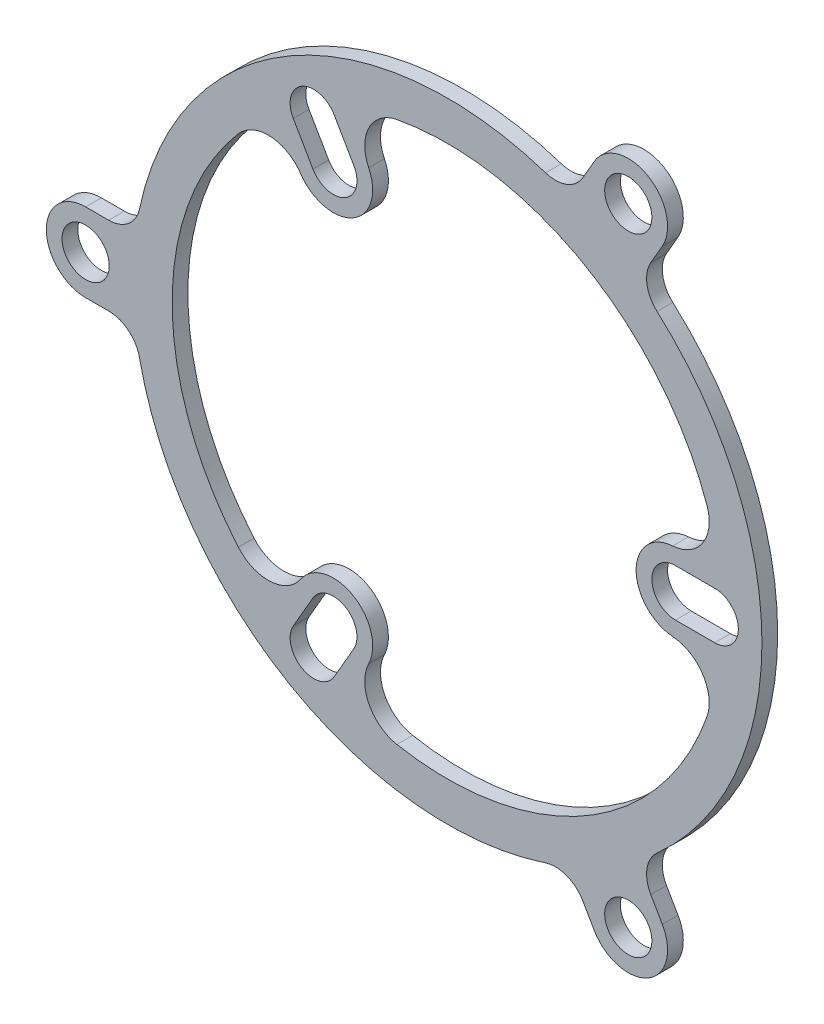
SolidWorks part; units mm, degrees
note: '?' marks a value the reader was unsure of.
material "1060 Alloy"
ref_plane "Front Plane" through (0, 0, 0) normal (0, 0, 1) x (1, 0, 0)
ref_plane "Top Plane" through (0, 0, 0) normal (0, 1, 0) x (1, 0, 0)
ref_plane "Right Plane" through (0, 0, 0) normal (1, 0, 0) x (0, 0, -1)
sketch "Sketch1" plane through (0, 0, 0) normal (0, 0, 1) x (1, 0, 0)
  circle A0 centre (0, 0) radius 40
  circle A1 centre (0, 0) radius 35
  dimension "D1" = 80
  dimension "D2" = 5
extrude "Boss-Extrude1" add sketch "Sketch1" along normal blind 2
sketch "Sketch2" plane through (0, 0, 0) normal (0, 0, -1) x (-1, 0, 0)
  line L0 (0, 0) -> (-40, 0) construction
  line L1 (-34, -3) -> (-29, -3)
  line L2 (-34, 3) -> (-29, 3)
  line L3 (-29, -5) -> (-34.641, -5)
  line L4 (-29, 5) -> (-34.641, 5)
  line L5 (-34.641, -5) -> (-37, -5)
  line L6 (-37, -5) -> (-37, 5)
  line L7 (-37, 5) -> (-34.641, 5)
  circle A0 centre (0, 0) radius 40 construction
  arc A1 (-34, 3) -> (-34, -3) centre (-34, 0) ccw
  arc A2 (-29, -3) -> (-29, 3) centre (-29, 0) ccw
  circle A3 centre (0, 0) radius 35 construction
  arc A4 (-29, -5) -> (-29, 5) centre (-29, 0) ccw
  circle M9 centre (0, 0) radius 35
  dimension "D1" = 6
  dimension "D2" = 34
  dimension "D3" = 5
  dimension "D4" = 2
extrude "Boss-Extrude2" add sketch "Sketch2" against normal blind 2 contours A4 L0 A2 L1 L3 M9 | L0 A4 L4 L2 A2 M9
sketch "Sketch3" plane through (0, 0, 0) normal (0, 0, -1) x (-1, 0, 0)
  circle A0 centre (-34, 0) radius 3
  arc A1 (-34, 3) -> (-34, -3) centre (-34, 0) ccw construction
  dimension "D1" = 6
extrude "Cut-Extrude1" cut sketch "Sketch3" against normal blind 2
fillet "Fillet1" radius 5 2 edges at (34.641, -5, 1) (34.641, 5, 1)
ref_axis "Axis1" through (0, 0, 2) along (0, 0, -1)?
pattern_circular "CirPattern1" count 3 over 360 about axis through (0, 0, 0) along (0, 0, 1) of "Boss-Extrude2", "Cut-Extrude1", "Fillet1"
sketch "Sketch4" plane through (0, 0, 0) normal (0, 0, -1) x (-1, 0, 0)
  line L0 (0, 0) -> (-40, 0) construction
  line L1 (0, 0) -> (20, 34.641) construction
  line L2 (0, 0) -> (-20, 34.641) construction
  line L3 (-20, 34.641) -> (-23, 39.8372) construction
  line L4 (-18.6699, 42.3372) -> (-15.513, 36.8693)
  line L5 (-27.3301, 37.3372) -> (-24.1733, 31.8693)
  line L6 (-27.3301, 37.3372) -> (-18.6699, 42.3372)
  line L7 (-24.1733, 31.8693) -> (-15.513, 36.8693)
  circle A0 centre (0, 0) radius 40 construction
  circle A1 centre (-23, 39.8372) radius 3
  arc A2 (-18.6699, 42.3372) -> (-27.3301, 37.3372) centre (-23, 39.8372) ccw
  circle M29 centre (0, 0) radius 40
  dimension "D3" = 6
  dimension "D5" = 2
  dimension "D1" = 120
  dimension "D2" = 60
  dimension "D4" = 6
extrude "Boss-Extrude3" add sketch "Sketch4" against normal blind 2 contours A1 L6 L5 L4 M29 | L6 A2 A1
fillet "Fillet2" radius 4 2 edges at (24.1733, 31.8693, 1) (15.513, 36.8693, 1)
pattern_circular "CirPattern2" count 3 over 360 about axis through (0, 0, 0) along (0, 0, 1) of "Boss-Extrude3", "Fillet2"
